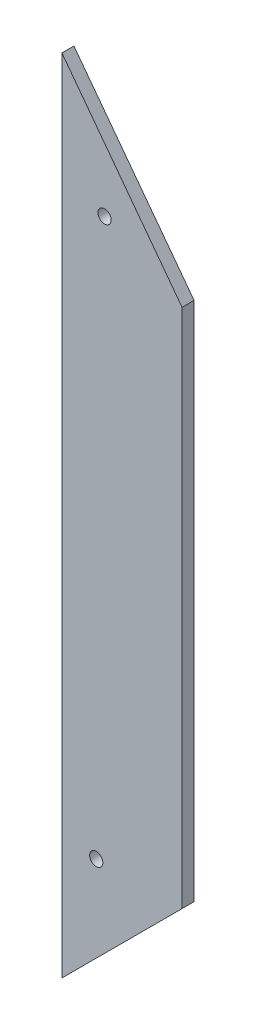
SolidWorks part; units mm, degrees
material "Акрил (Средняя-высокая ударопрочность)"
ref_plane "Спереди" through (0, 0, 0) normal (0, 0, 1) x (1, 0, 0)
ref_plane "Сверху" through (0, 0, 0) normal (0, 1, 0) x (1, 0, 0)
ref_plane "Справа" through (0, 0, 0) normal (1, 0, 0) x (0, 0, -1)
sketch "Эскиз1" plane through (0, 0, 0) normal (0, 0, 1) x (1, 0, 0)
  line L0 (0, 0) -> (0, 200)
  line L1 (0, 0) -> (30, 30)
  line L2 (30, 30) -> (30, 160)
  line L3 (30, 160) -> (0, 200)
  dimension "D1" = 200
  dimension "D2" = 30
  dimension "D3" = 40
  dimension "D4" = 30
extrude "Бобышка-Вытянуть1" add sketch "Эскиз1" along normal blind 3
sketch "Эскиз3" plane through (0, 0, 0) normal (-1, 0, 0) x (0, 0, 1)
  line L0 (1.5, 200) -> (1.5, -113.6649) construction
  line L1 (3, 200) -> (0, 200) construction
sketch "Эскиз4" plane through (30, 0, 0) normal (1, 0, 0) x (0, 0, -1)
  line L0 (-1.5, 160) -> (-1.5, -28.0184) construction
  line L1 (-3, 160) -> (0, 160) construction
extrude "Вырез-Вытянуть1" cut sketch "Эскиз5" against normal blind 8 contours L4 A0 | A0 L4 | A1 region at (9.955, 170.0104, -1.5) region at (11.3554, 169.9896, -1.5) region at (8.5714, 30.0155, -1.5)
sketch "Эскиз5" plane through (-305.9612, -184.2045, -1.5) normal (0, 0, -1) x (-0.9999, 0.0149, 0)
  line L0 (-300.2088, 388.7158) -> (-304.8774, 75.0857) construction
  line L2 (-317.5586, 363.9713) -> (-305.06, 363.7853)
  line L3 (-317.7074, 353.9725) -> (-305.2088, 353.7864)
  line L4 (-311.3093, 363.8783) -> (-311.3093, 353.8772) construction
  circle A0 centre (-311.3093, 358.8778) radius 1.65
  circle A1 centre (-311.3093, 218.8778) radius 1.65
  dimension "D1" = 10.6552
  dimension "D2" = 29.8381
  dimension "D3" = 2
